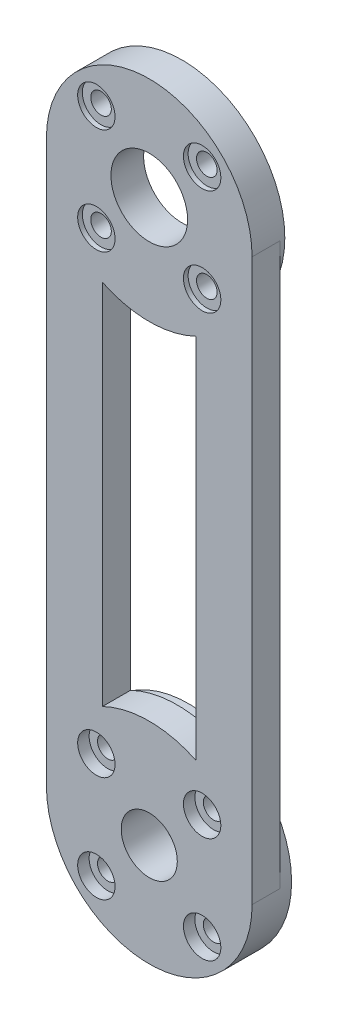
SolidWorks part; units mm, degrees
ref_plane "Front Plane" through (0, 0, 0) normal (0, 0, 1) x (1, 0, 0)
ref_plane "Top Plane" through (0, 0, 0) normal (0, 1, 0) x (1, 0, 0)
ref_plane "Right Plane" through (0, 0, 0) normal (1, 0, 0) x (0, 0, -1)
sketch "Sketch1" plane through (0, 0, 0) normal (0, 0, 1) x (1, 0, 0)
  line L0 (0, 30) -> (0, -30) construction
  line L2 (11, 30) -> (11, -30)
  line L4 (-11, 30) -> (-11, -30)
  line L7 (-5, 19.6438) -> (-5, -19.6438)
  line L9 (5, 19.6438) -> (5, -19.6438)
  circle A0 centre (0, 30) radius 11
  circle A1 centre (0, -30) radius 11
  arc A2 (-5, 19.6438) -> (5, 19.6438) centre (0, 30) ccw
  arc A3 (5, -19.6438) -> (-5, -19.6438) centre (0, -30) ccw
  point P0 (0, 0)
  point P2 (0, 0)
  point P17 (0, 0)
  point P18 (0, 0)
  point P19 (0, 0)
  dimension "D3" = 22
  dimension "D1" = 60
  dimension "D4" = 23
  dimension "D5" = 6
  dimension "D2" = 22
  dimension "D6" = 6
extrude "Boss-Extrude1" add sketch "Sketch1" along normal blind 3 contours A1 L2 A0 L4 | A0 | A1 | A0 L0 A1 L2 region at (0, 30, 0) region at (10.3609, 0, 0) region at (0, -30, 0)
extrude "Boss-Extrude2" add sketch "Sketch1<3>" against normal blind 0.5 contours A0 region at (0, 30, 0)
sketch "Sketch1<3>" plane through (0, 0, 0) normal (0, 0, 1) x (1, 0, 0) same geometry as "Sketch1"
sketch "Sketch2" plane through (0, 0, 3) normal (0, 0, 1) x (1, 0, 0)
  line L0 (0, 30) -> (5.6569, 35.6569) construction
  line L1 (11, 30) -> (11, -30) construction
  circle A0 centre (0, 30) radius 4.1
  circle A1 centre (5.6569, 35.6569) radius 1.1
  circle A2 centre (5.6569, 35.6569) radius 2
  dimension "D1" = 8.2
  dimension "D2" = 2.2
  dimension "D5" = 4
  dimension "D3" = 8
  dimension "D4" = 45
extrude "Cut-Extrude1" cut sketch "Sketch2" against normal up to surface (3.5 mm away) contours A0 | A1 region at (0, 30, 3) region at (5.6569, 35.6569, 3) up to face at (11, 30, -0.5)
extrude "Cut-Extrude2" cut sketch "Sketch2<3>" against normal offset from surface (0.5 mm away) 3 contours A2 A1 region at (3.7134, 35.6569, 3) up to face at (4.1, 30, -0.5)
sketch "Sketch2<3>" plane through (0, 0, 3) normal (0, 0, 1) x (1, 0, 0) same geometry as "Sketch2"
pattern_circular "CirPattern2" count 4 over 360 about axis through (0, 30, 3) along (0, 0, 1) of "Cut-Extrude2", "Cut-Extrude1"
extrude "Boss-Extrude3" add sketch "Sketch1<5>" against normal blind 1.225 contours A1 region at (0, -30, 0)
sketch "Sketch1<5>" plane through (0, 0, 0) normal (0, 0, 1) x (1, 0, 0) same geometry as "Sketch1"
sketch "Sketch3" plane through (0, 0, 3) normal (0, 0, 1) x (1, 0, 0)
  line L0 (5.6569, -24.3431) -> (0, -30) construction
  line L1 (11, 30) -> (11, -30) construction
  circle A0 centre (0, -30) radius 3
  circle A1 centre (5.6569, -24.3431) radius 1.1
  circle A2 centre (5.6569, -24.3431) radius 2
  dimension "D2" = 6
  dimension "D3" = 2.2
  dimension "D5" = 4
  dimension "D1" = 45
  dimension "D4" = 8
extrude "Cut-Extrude3" cut sketch "Sketch3" against normal up to surface (4.225 mm away) contours A0 | A1 region at (0, -30, 3) up to face at (11, -30, -1.225)
extrude "Cut-Extrude4" cut sketch "Sketch3<3>" against normal offset from surface (1.225 mm away) 3 contours A1 A2 region at (3.7134, -24.3431, 3) up to face at (3, -30, -1.225)
sketch "Sketch3<3>" plane through (0, 0, 3) normal (0, 0, 1) x (1, 0, 0) same geometry as "Sketch3"
pattern_circular "CirPattern3" count 4 over 360 about axis through (0, -30, 3) along (0, 0, 1) of "Cut-Extrude4", "Cut-Extrude3"
